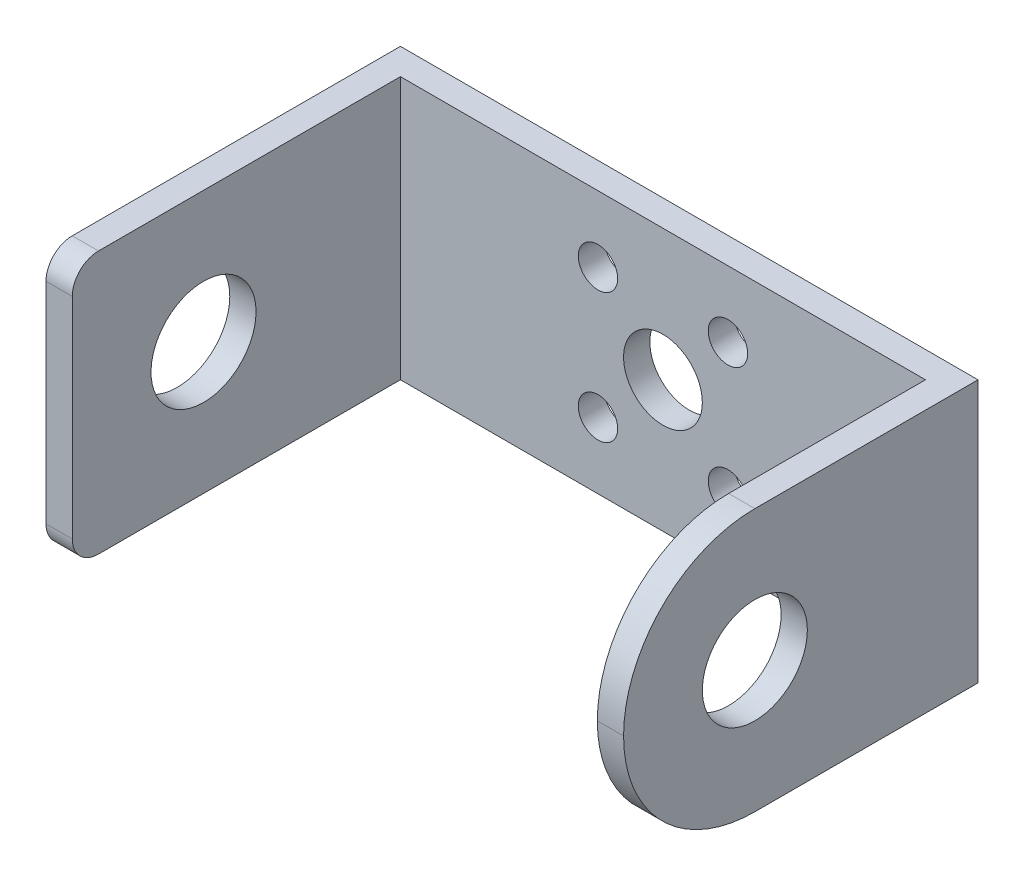
SolidWorks part; units mm, degrees
ref_plane "Alzado" through (0, 0, 0) normal (0, 0, 1) x (1, 0, 0)
ref_plane "Planta" through (0, 0, 0) normal (0, 1, 0) x (1, 0, 0)
ref_plane "Vista lateral" through (0, 0, 0) normal (1, 0, 0) x (0, 0, -1)
sketch "Croquis1" plane through (0, 0, 0) normal (0, 0, 1) x (1, 0, 0)
  line L1 (-22, -10) -> (22, -10)
  line L2 (-22, -10) -> (-22, 10)
  line L3 (-22, 10) -> (22, 10)
  line L4 (22, -10) -> (22, 10)
  line L5 (-22, -10) -> (22, 10) construction
  line L6 (-22, 10) -> (22, -10) construction
  point P0 (0, 0)
  dimension "D1" = 44
  dimension "D2" = 20
extrude "Saliente-Extruir1" add sketch "Croquis1" along normal blind 2
sketch "Croquis2" plane through (0, 0, 2) normal (0, 0, 1) x (1, 0, 0)
  line L0 (0, 10) -> (0, -10) construction
  line L1 (22, 10) -> (-22, 10) construction
  line L2 (-22, -10) -> (22, -10) construction
  line L3 (-22, 0) -> (22, 0) construction
  line L4 (-22, 10) -> (-22, -10) construction
  line L5 (22, -10) -> (22, 10) construction
  line L6 (0, 0) -> (-7.1442, 7.1442) construction
  circle A0 centre (0, 0) radius 3
  circle A1 centre (-4.9497, 4.9497) radius 1.5
  circle A2 centre (4.9497, 4.9497) radius 1.5
  circle A3 centre (4.9497, -4.9497) radius 1.5
  circle A4 centre (-4.9497, -4.9497) radius 1.5
  dimension "D1" = 6
  dimension "D2" = 3
  dimension "D3" = 7
extrude "Cortar-Extruir1" cut sketch "Croquis2" against normal blind 2
sketch "Croquis3" plane through (0, 0, 2) normal (0, 0, 1) x (1, 0, 0)
  line L0 (-22, -10) -> (22, -10) construction
  line L1 (-22, 10) -> (-20, 10)
  line L2 (-22, 10) -> (-22, -10)
  line L3 (-22, -10) -> (-20, -10)
  line L4 (-20, 10) -> (-20, -10)
  line L6 (22, 10) -> (20, 10)
  line L7 (22, 10) -> (22, -10)
  line L8 (22, -10) -> (20, -10)
  line L9 (20, 10) -> (20, -10)
  dimension "D1" = 2
  dimension "D2" = 2
extrude "Saliente-Extruir2" add sketch "Croquis3" along normal blind 25
fillet "Redondeo1" radius 10 2 edges at (21, 10, 27) (21, -10, 27)
fillet "Redondeo2" radius 2 2 edges at (-21, 10, 27) (-21, -10, 27)
sketch "Croquis4" plane through (22, 0, 0) normal (1, 0, 0) x (0, 0, -1)
  line L0 (0, 0) -> (-31.1047, 0) construction
  line L1 (0, -10) -> (0, 10) construction
  circle A0 centre (-17, 0) radius 4
  dimension "D1" = 8
  dimension "D2" = 10
extrude "Cortar-Extruir2" cut sketch "Croquis4" against normal up to surface (44 mm away) up to face at (-22, 0, 17.4714)
